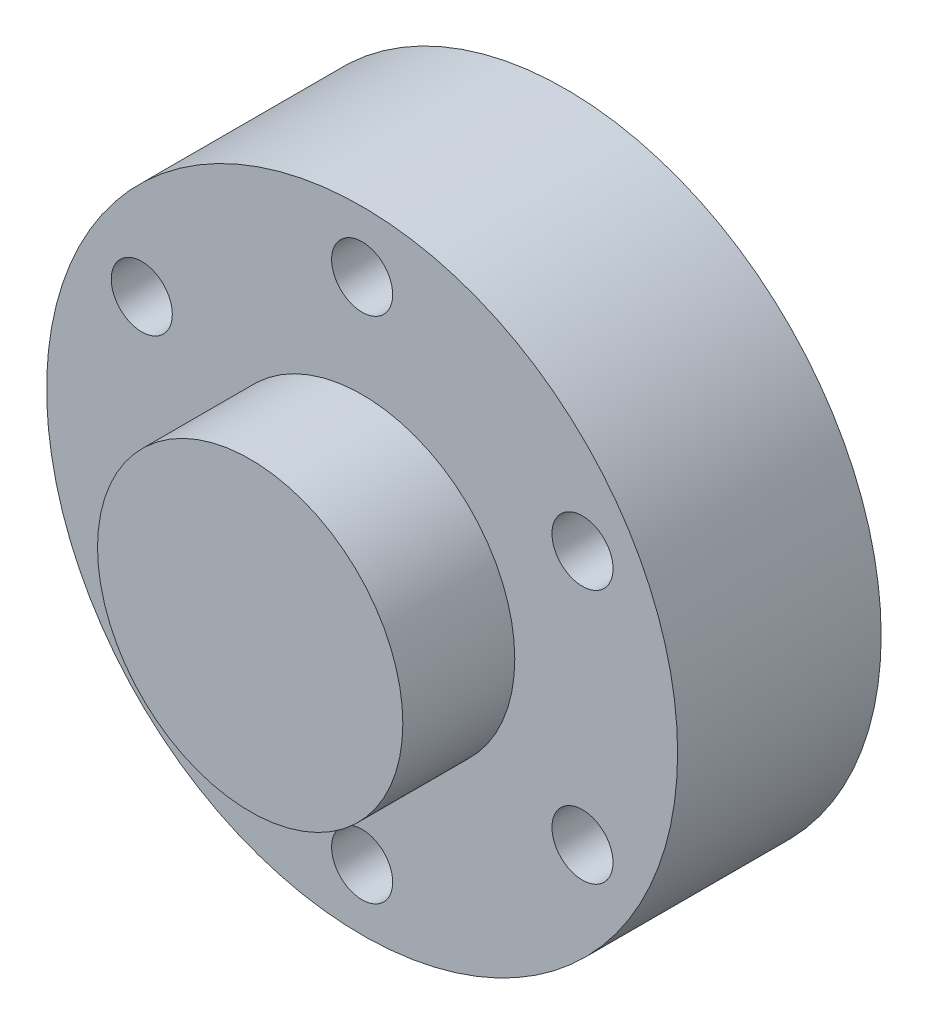
SolidWorks part; units mm, degrees
ref_plane "Front Plane" through (0, 0, 0) normal (0, 0, 1) x (1, 0, 0)
ref_plane "Top Plane" through (0, 0, 0) normal (0, 1, 0) x (1, 0, 0)
ref_plane "Right Plane" through (0, 0, 0) normal (1, 0, 0) x (0, 0, -1)
sketch "Sketch2" plane through (0, 0, 0) normal (0, 0, 1) x (1, 0, 0)
  line L0 (0, 20.3178) -> (0, -21.083) construction
  circle A0 centre (0, 0) radius 9.5
  circle A1 centre (0, 0) radius 12.5 construction
  circle A3 centre (0, 0) radius 15.5
  circle A4 centre (0, 12.5) radius 1.5
  circle A5 centre (10.8253, 6.25) radius 1.5
  circle A6 centre (10.8253, -6.25) radius 1.5
  circle A7 centre (0, -12.5) radius 1.5
  circle A8 centre (-10.8253, -6.25) radius 1.5
  circle A9 centre (-10.8253, 6.25) radius 1.5
  point P21 (1.7321, -1)
  point P22 (0, 0)
  dimension "D1" = 19
  dimension "D2" = 6
  dimension "D3" = 25
  dimension "D4" = 31
  dimension "D5" = 3
extrude "Boss-Extrude1" add sketch "Sketch2" along normal blind 10 contours A3 A9 A8 A7 A6 A5 A4 A0 | A0 region at (0, 0, 0) region at (-15.0616, 0, 0)
sketch "Sketch3" plane through (0, 0, 10) normal (0, 0, 1) x (1, 0, 0)
  circle A0 centre (0, 0) radius 7.5
  dimension "D1" = 15
extrude "Boss-Extrude2" add sketch "Sketch3" along normal blind 5.5
sketch "Sketch6" plane through (0, 0, 0) normal (0, 0, -1) x (-1, 0, 0)
  circle A0 centre (0, 0) radius 7.5
  dimension "D1" = 15
extrude "Boss-Extrude4" add sketch "Sketch6" along normal blind 5.5 contours A0
sketch "Sketch7" plane through (0, 0, -5.5) normal (0, 0, -1) x (-1, 0, 0)
  circle A0 centre (0, 0) radius 2
  dimension "D1" = 4
extrude "Boss-Extrude5" add sketch "Sketch7" along normal blind 1
fillet "Fillet2" radius 0.05 1 edges at (-2, 0, -6.5)
sketch "Sketch9" plane through (0, 0, -6.5) normal (0, 0, -1) x (-1, 0, 0)
  line L1 (-1.2247, 1.25) -> (1.2247, 1.25)
  arc A0 (-1.2247, 1.25) -> (1.2247, 1.25) centre (0, 0) ccw
  circle A1 centre (0, -0.25) radius 1.5 construction
  dimension "D1" = 3.5
  dimension "D2" = 3
extrude "Cut-Extrude1" cut sketch "Sketch9" against normal blind 11
